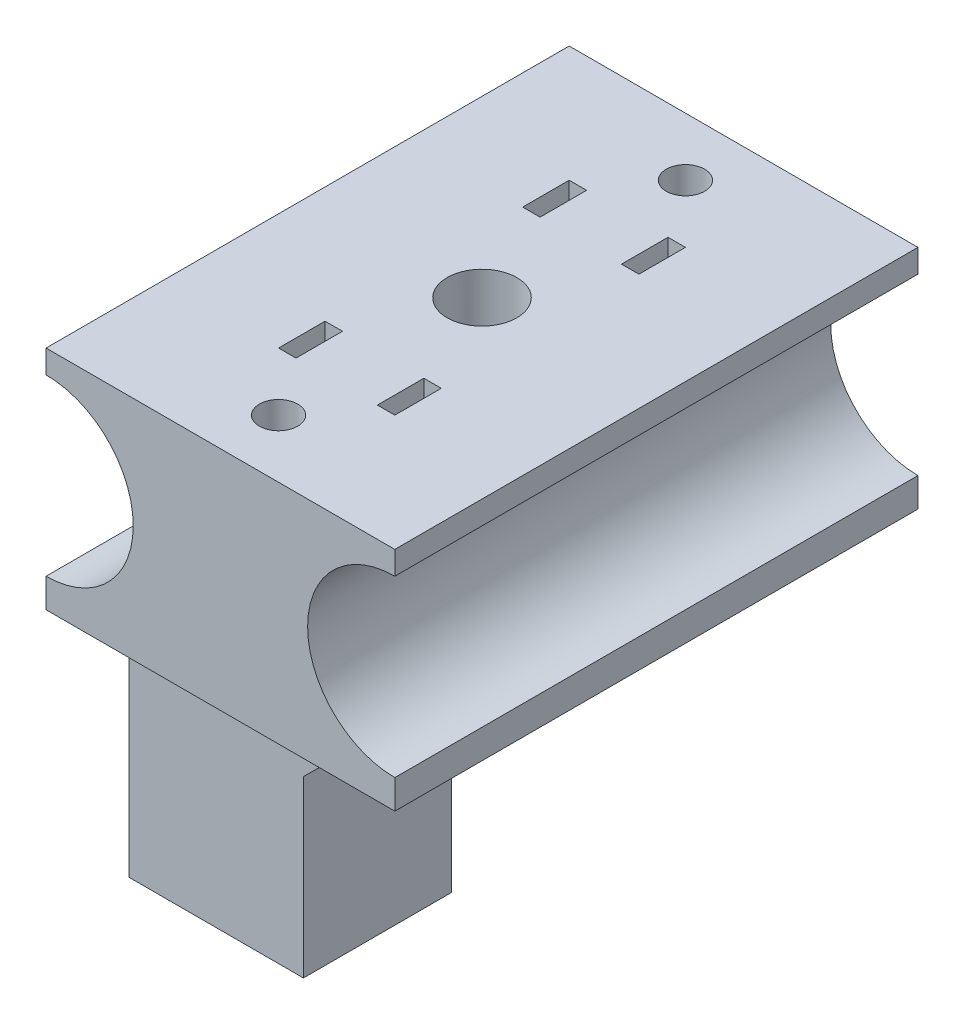
SolidWorks part; units mm, degrees
material "ABS"
ref_plane "Front Plane" through (0, 0, 0) normal (0, 0, 1) x (1, 0, 0)
ref_plane "Top Plane" through (0, 0, 0) normal (0, 1, 0) x (1, 0, 0)
ref_plane "Right Plane" through (0, 0, 0) normal (1, 0, 0) x (0, 0, -1)
sketch "Sketch1" plane through (0, 0, 0) normal (0, 0, 1) x (1, 0, 0)
  line L0 (15, 0) -> (-15, 0) construction
  line L5 (-15, 7.5) -> (-15, 9.5)
  line L6 (-15, 9.5) -> (15, 9.5)
  line L7 (15, 7.5) -> (15, 9.5)
  line L9 (-15, -7.5) -> (-15, -10)
  line L10 (-15, -10) -> (15, -10)
  line L11 (15, -7.5) -> (15, -10)
  arc A0 (15, 7.5) -> (15, -7.5) centre (15, 0) ccw
  arc A1 (-15, -7.5) -> (-15, 7.5) centre (-15, 0) ccw
  point P8 (0, 0)
  dimension "D2" = 15
  dimension "D1" = 30
  dimension "D3" = 2.5
  dimension "D4" = 2
extrude "Boss-Extrude1" add sketch "Sketch1" along normal mid plane 45
sketch "Sketch3" plane through (0, 0, 0) normal (0, 0, 1) x (1, 0, 0)
  line L0 (0, 9.5) -> (0, -10)
  line L1 (0, -10) -> (8, -10)
  line L2 (8, -10) -> (8, -3.25)
  line L3 (8, -3.25) -> (6, -3.25)
  line L4 (6, -3.25) -> (6, 2.75)
  line L5 (6, 2.75) -> (8, 2.75)
  line L6 (8, 2.75) -> (8, 9.5)
  line L7 (8, 9.5) -> (0, 9.5)
  line L8 (15, 9.5) -> (-15, 9.5) construction
  line L9 (-15, -10) -> (15, -10) construction
  dimension "D1" = 6
  dimension "D2" = 8
  dimension "D3" = 6
revolve "Cut-Revolve1" [suppressed] cut sketch "Sketch3" angle 360 about L0
hole_wizard "M4x0.7 Tapped Hole2" positions "Sketch5" profile "Sketch4" tap size "M4x0.7" standard "ANSI Metric" end condition through all
sketch "Sketch5" plane through (0, -10, 0) normal (0, -1, 0) x (-1, 0, 0)
  line L0 (0, 17.5) -> (0, -17.5) construction
  line L2 (15, -22.5) -> (-15, -22.5) construction
  point P0 (0, -17.5)
  point P2 (0, 17.5)
  dimension "D1" = 5
sketch "Sketch4" plane through (0, -10, 17.5) normal (1, 0, 0) x (0, 0, -1)
  line L0 (0, 0) -> (0, 19.5)
  line L1 (0, 19.5) -> (1.65, 19.5)
  line L2 (1.65, 19.5) -> (1.65, 0)
  line L5 (1.65, 0) -> (0, 0)
  line L11 (0, -6.35) -> (0, 107.95) construction
  dimension "Thru Tap Drill Dia." = 3.3
  dimension "Thru Tap Drill Depth" = 19.5
cosmetic thread "Hole Thread1" parameters "D2"=4
cosmetic thread "Hole Thread2" parameters "D2"=4
sketch "Sketch7" plane through (0, 0, 0) normal (0, 0, 1) x (1, 0, 0)
  line L0 (-15, -7.5) -> (-24, -7.5)
  line L1 (-24, -7.5) -> (-24, -42.5)
  line L5 (8.5, -10) -> (-15, -10)
  line L6 (-15, -10) -> (-15, -7.5)
  line L7 (-24, -42.5) -> (-9, -42.5)
  line L8 (-9, -42.5) -> (-9, -27.5)
  line L9 (-9, -27.5) -> (8.5, -10)
  dimension "D1" = 9
  dimension "D2" = 35
  dimension "D3" = 15
  dimension "D4" = 45
  dimension "D6" = 15
extrude "Boss-Extrude3" add sketch "Sketch7" against normal mid plane 12.725
hole_wizard "M4x0.7 Tapped Hole1" positions "Sketch9" profile "Sketch8" tap size "M4x0.7" standard "ANSI Metric"
sketch "Sketch9" plane through (-24, 0, 0) normal (1, 0, 0) x (0, 0, -1)
  line L0 (6.3625, -42.5) -> (-6.3625, -42.5) construction
  point P0 (0, -37.5)
  point P2 (0, -22.5)
  dimension "D1" = 15
  dimension "D2" = 5
sketch "Sketch8" plane through (-24, -37.5, 0) normal (0, 1, 0) x (0, 0, 1)
  line L0 (0, 0) -> (0, 10.9914)
  line L1 (0, 10.9914) -> (1.65, 10)
  line L2 (1.65, 10) -> (1.65, 0)
  line L5 (1.65, 0) -> (0, 0)
  line L10 (0, 10.9914) -> (-1.65, 10) construction
  line L11 (0, -6.35) -> (0, 107.95) construction
  dimension "Tap Drill Dia." = 3.3
  dimension "Tap Drill Depth" = 10
  dimension "Drill Angle" = 118
cosmetic thread "Hole Thread5" parameters "D1"=8, "D2"=4
cosmetic thread "Hole Thread6" parameters "D1"=8, "D2"=4
sketch "Sketch10" plane through (0, 0, -6.3625) normal (0, 0, -1) x (-1, 0, 0)
  line L0 (15, -10) -> (24, -19)
  line L1 (24, -7.5) -> (24, -42.5) construction
  line L2 (24, -19) -> (24, -7.5)
  line L3 (24, -7.5) -> (15, -7.5)
  line L4 (15, -7.5) -> (15, -10)
  dimension "D1" = 45
extrude "Cut-Extrude2" cut sketch "Sketch10" against normal blind 85
sketch "Sketch2" plane through (0, 9.5, 0) normal (0, 1, 0) x (1, 0, 0)
  circle A0 centre (0, 0) radius 3
  dimension "D1" = 6
extrude "Cut-Extrude1" cut sketch "Sketch2" against normal blind 50
sketch "Sketch11" plane through (0, 0, -22.5) normal (0, 0, -1) x (-1, 0, 0)
  line L0 (-5, 9.5) -> (-5, 0)
  line L1 (-15, 9.5) -> (15, 9.5) construction
  line L3 (-15, -10) -> (-3.5, -10)
  line L4 (15, -10) -> (-15, -10) construction
  line L5 (-3.5, -10) -> (-3.5, 9.5)
  line L6 (-3.5, 9.5) -> (-5, 9.5)
  line L7 (0, 9.5) -> (0, -10) construction
  line L8 (3.5, 9.5) -> (5, 9.5)
  line L9 (3.5, -10) -> (3.5, 9.5)
  line L10 (15, -10) -> (3.5, -10)
  line L11 (5, 9.5) -> (5, 0)
  arc A0 (-5, 0) -> (-15, -10) centre (-15, 0) cw
  arc A1 (5, 0) -> (15, -10) centre (15, 0) ccw
  arc A3 (-15, -7.5) -> (-15, 7.5) centre (-15, 0) ccw construction
  line M5 (-15, -7.5) -> (-15, -10)
  line M6 (-15, -10) -> (15, -10)
  line M7 (15, -10) -> (15, -7.5)
  line M10 (15, 9.5) -> (-15, 9.5)
  dimension "D2" = 1.5
extrude "Cut-Extrude3" cut sketch "Sketch11" against normal blind 4 from offset 10 contours A1 L11 L9 M10 M6 M7 | L0 A0 L5 M5 M6 M10 region at (5.5127, -3.4309, -22.5) region at (-5.5127, -3.4309, -22.5) offset against normal yes
mirror "Mirror1" about plane through (0, 0, 0) normal (0, 0, 1) of "Cut-Extrude3"
